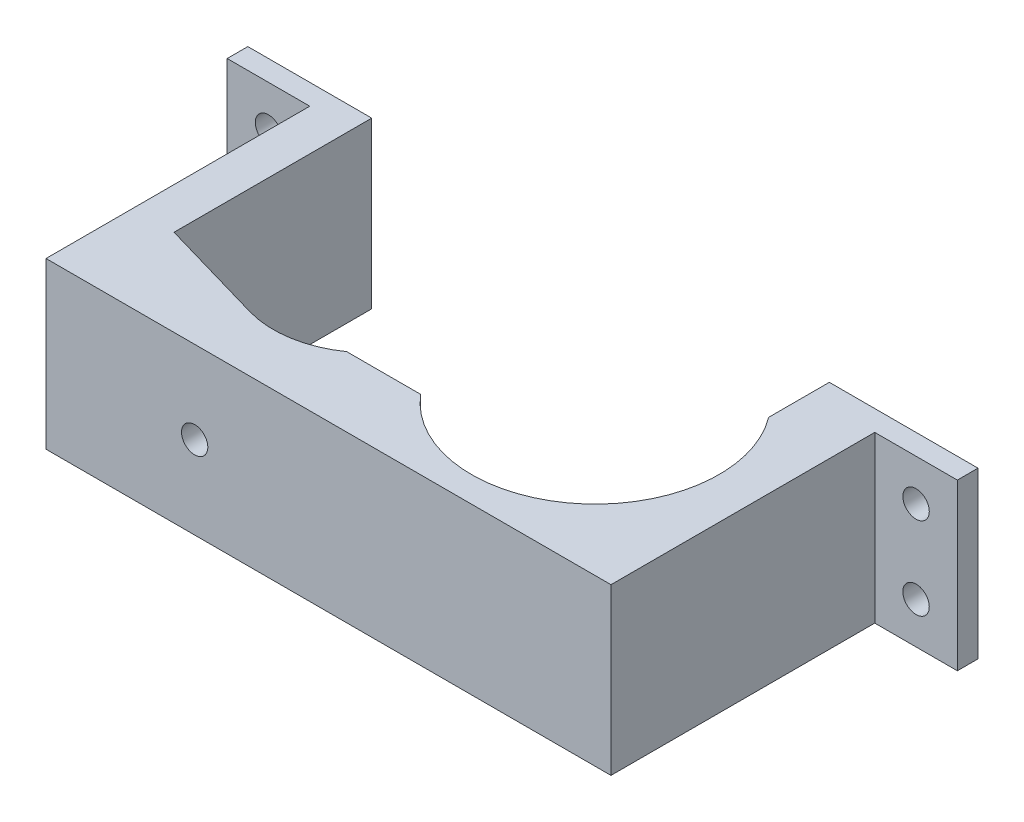
SolidWorks part; units mm, degrees
ref_plane "Front Plane" through (0, 0, 0) normal (0, 0, 1) x (1, 0, 0)
ref_plane "Top Plane" through (0, 0, 0) normal (0, 1, 0) x (1, 0, 0)
ref_plane "Right Plane" through (0, 0, 0) normal (1, 0, 0) x (0, 0, -1)
sketch "Sketch1" plane through (0, 0, 0) normal (0, 1, 0) x (1, 0, 0)
  line L0 (-20.574, -9.6521) -> (-4.162, -14.3967)
  line L1 (-4.1621, 14.3967) -> (-20.574, 9.652) construction
  line L2 (-20.574, 9.652) -> (-20.574, -9.6521)
  line L3 (-39.624, 20.7467) -> (-20.574, 20.7467)
  line L4 (-39.624, 20.7467) -> (-39.624, 17.5717)
  line L6 (49.784, 20.7467) -> (72.644, 20.7467)
  line L7 (-39.624, 17.5717) -> (-26.924, 17.5717)
  line L9 (-26.924, 17.5717) -> (-26.924, -12.8271)
  line L10 (72.644, 20.7467) -> (72.644, 17.5717)
  line L11 (72.644, 17.5717) -> (59.944, 17.5717)
  line L12 (59.944, 17.5717) -> (59.944, -12.8271)
  line L13 (-20.574, 9.652) -> (-20.574, 20.7467)
  line L15 (59.944, -12.8271) -> (59.944, -22.9871)
  line L16 (59.944, -22.9871) -> (-26.924, -22.9871)
  line L17 (-26.924, -22.9871) -> (-26.924, -12.8271)
  line L18 (53.594, 0) -> (53.594, 36.7061) construction
  line L19 (49.784, 20.7467) -> (49.784, 11.43)
  line L20 (8.5997, -12.2733) -> (19.9745, -12.2733)
  arc A0 (-4.162, -14.3967) -> (8.5997, -12.2733) centre (0, 0) ccw
  arc A1 (-26.924, -12.8271) -> (59.944, -12.8271) centre (16.51, -3.3778) ccw construction
  arc A2 (14.9527, -1.0034) -> (-4.1621, 14.3967) centre (0, 0) ccw construction
  arc A3 (8.5997, -12.2733) -> (14.9527, -1.0034) centre (0, 0) ccw construction
  arc A4 (49.784, 11.43) -> (19.9745, -12.2733) centre (34.544, 0) ccw construction
  circle A5 centre (34.544, 0) radius 19.05 construction
  arc A6 (19.9745, -12.2733) -> (49.784, 11.43) centre (34.544, 0) ccw
  point P16 (61.214, 20.7467)
  dimension "D2" = 14.9863
  dimension "D14" = 6.35
  dimension "D10" = 44.45
  dimension "D1" = 19.3041
  dimension "D3" = 16.4119
  dimension "D4" = 106.124
  dimension "D5" = 20.574
  dimension "D6" = 106.125
  dimension "D7" = 6.35
  dimension "D8" = 6.35
  dimension "D9" = 3.175
  dimension "D11" = 12.7
  dimension "D12" = 3.175
  dimension "D13" = 3.81
  dimension "D15" = 10.16
  dimension "D16" = 33.02
extrude "Boss-Extrude1" add sketch "Sketch1" along normal blind 25.4
sketch "Sketch2" plane through (0, 0, -17.5717) normal (0, 0, 1) x (1, 0, 0)
  line L0 (-39.624, 0) -> (-26.924, 0) construction
  line L1 (-39.624, 25.4) -> (-39.624, 0) construction
  line L2 (-39.624, 25.4) -> (-26.924, 25.4) construction
  line L3 (72.644, 25.4) -> (72.644, 0) construction
  circle A0 centre (-33.274, 19.05) radius 2.032
  circle A1 centre (-33.274, 6.35) radius 2.032
  circle A2 centre (66.294, 19.05) radius 2.032
  circle A3 centre (66.294, 6.35) radius 2.032
  dimension "D5" = 4.064
  dimension "D1" = 6.35
  dimension "D2" = 6.35
  dimension "D3" = 6.35
  dimension "D4" = 6.35
sketch "Sketch6" plane through (0, 0, -20.7467) normal (0, 0, -1) x (-1, 0, 0)
  line L0 (-72.644, 0) -> (-49.784, 0) construction
  line L1 (-72.644, 25.4) -> (-72.644, 0) construction
  line L2 (-72.644, 25.4) -> (-49.784, 25.4) construction
  line L4 (39.624, 25.4) -> (39.624, 0) construction
  circle A0 centre (-66.294, 6.35) radius 2.032
  circle A1 centre (-66.294, 19.05) radius 2.032
  circle A2 centre (33.274, 6.35) radius 2.032
  circle A3 centre (33.274, 19.05) radius 2.032
  point P14 (0, 0)
  point P17 (0, 0)
  dimension "D1" = 4.064
  dimension "D2" = 6.35
  dimension "D3" = 6.35
  dimension "D4" = 6.35
  dimension "D5" = 6.35
extrude "Cut-Extrude1" cut sketch "Sketch2" against normal through all
sketch "Sketch3" plane through (0, 0, 22.9871) normal (0, 0, 1) x (1, 0, 0)
  line L0 (-26.924, 25.4) -> (59.944, 25.4) construction
  line L1 (-26.924, 25.4) -> (-26.924, 0) construction
  circle A0 centre (-4.064, 12.7) radius 1.905
  dimension "D3" = 3.81
  dimension "D1" = 12.7
  dimension "D2" = 22.86
hole_wizard "#10-32 Tapped Hole1" positions "Sketch4" profile "Sketch5" tap size "#10-32" standard "ANSI Inch" end condition through all
sketch "Sketch4" plane through (0, 0, 22.9871) normal (0, 0, 1) x (1, 0, 0)
  point P0 (-4.064, 12.7)
sketch "Sketch5" plane through (-4.064, 12.7, 22.9871) normal (1, 0, 0) x (0, -1, 0)
  line L0 (0, 0) -> (0, 43.7338)
  line L1 (0, 43.7338) -> (2.0193, 43.7338)
  line L2 (2.0193, 43.7338) -> (2.0193, 0)
  line L5 (2.0193, 0) -> (0, 0)
  line L11 (0, -6.35) -> (0, 107.95) construction
  dimension "Thru Tap Drill Dia." = 4.0386
  dimension "Thru Tap Drill Depth" = 43.7338
cosmetic thread "Hole Thread1" parameters "D2"=4.826
